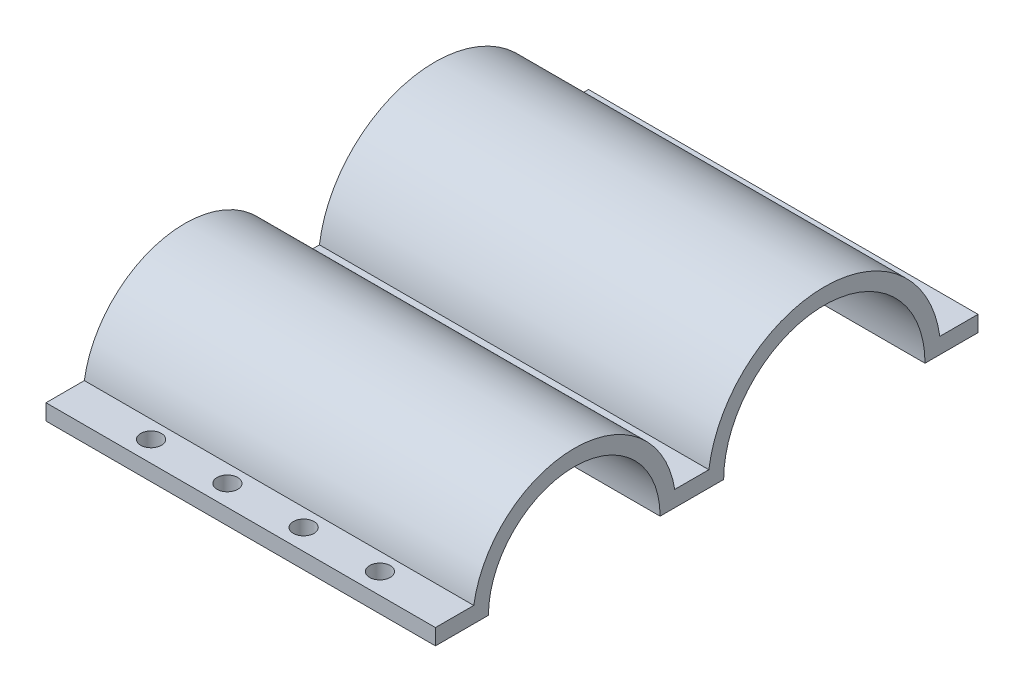
SolidWorks part; units mm, degrees
ref_plane "Front Plane" through (0, 0, 0) normal (0, 0, 1) x (1, 0, 0)
ref_plane "Top Plane" through (0, 0, 0) normal (0, 1, 0) x (1, 0, 0)
ref_plane "Right Plane" through (0, 0, 0) normal (1, 0, 0) x (0, 0, -1)
sketch "Sketch2" plane through (0, 0, 0) normal (1, 0, 0) x (0, 0, -1)
  line L0 (0, 0) -> (-10, 0)
  line L1 (-102.4, 0) -> (-102.4, 3)
  line L3 (0, 3) -> (0, 0)
  line L4 (-48, 0) -> (-60, 0)
  line L5 (-92.4, 0) -> (-102.4, 0)
  line L6 (0, 3) -> (-7.2055, 3)
  line L7 (-50.7945, 3) -> (-57.2358, 3)
  line L8 (-95.1642, 3) -> (-102.4, 3)
  arc A0 (-60, 0) -> (-92.4, 0) centre (-76.2, 0) ccw
  arc A1 (-10, 0) -> (-48, 0) centre (-29, 0) ccw
  arc A2 (-7.2055, 3) -> (-50.7945, 3) centre (-29, 0) ccw
  arc A3 (-57.2358, 3) -> (-95.1642, 3) centre (-76.2, 0) ccw
  dimension "D2" = 16.2
  dimension "D4" = 19
  dimension "D3" = 10
  dimension "D1" = 12
  dimension "D6" = 3
extrude "Boss-Extrude1" add sketch "Sketch2" along normal blind 73.5
sketch "Sketch3" plane through (0, 3, 0) normal (0, 1, 0) x (1, 0, 0)
  line L1 (73.5, 0) -> (0, 0) construction
  line L2 (73.5, -3.93) -> (1.5, -3.93) construction
  line L6 (73.5, -102.4) -> (0, -102.4) construction
  line L7 (0, -60) -> (0, -48) construction
  line L8 (0, -54) -> (85.8213, -54) construction
  line L9 (0, -98.47) -> (85.8213, -98.47) construction
  line L10 (0, -60) -> (0, -48) construction
  circle A0 centre (15.9, -3.93) radius 1.95
  circle A1 centre (30.3, -3.93) radius 1.95
  circle A2 centre (44.7, -3.93) radius 1.95
  circle A3 centre (59.1, -3.93) radius 1.95
  circle A4 centre (15.9, -54) radius 1.95
  circle A5 centre (30.3, -54) radius 1.95
  circle A6 centre (44.7, -54) radius 1.95
  circle A7 centre (59.1, -54) radius 1.95
  circle A8 centre (15.9, -98.47) radius 1.95
  circle A9 centre (30.3, -98.47) radius 1.95
  circle A10 centre (44.7, -98.47) radius 1.95
  circle A11 centre (59.1, -98.47) radius 1.95
  point P40 (0, -54)
  dimension "D1" = 3.9
  dimension "D4" = 14.4
  dimension "D5" = 14.4
  dimension "D6" = 14.4
  dimension "D2" = 72
  dimension "D3" = 14.4
  dimension "D7" = 3.93
  dimension "D8" = 3.93
extrude "Cut-Extrude1" cut sketch "Sketch3" against normal up to surface (3 mm away) up to face at (36.75, 0, 97.4)
equation "\"MotorDIA\"= 37'ME 405 Motor Diameter"
equation "\"SyringeDIA\"= 31.4'60ml Syringe Diameter"
equation "\"MotorShaftDIA\"= 6'Motor Shaft Dia"
equation "\"MotorKeyway\"= 1'ME 405 Motor Shaft Keyway Depth"
equation "\"MotorLength\"= 67.5'ME 405 Motor Length Excluding Shaft"
equation "\"SyringeLength\"= 117.3'60ml Syringe Length Excluding Nozzle"
equation "\"3Dtol\"= .5'Sizing Tolerance for 3D printed parts"
equation "\"ChamberDIA\"= 100 - 4'Buoyancy Chamber inner Diameter"
equation "\"ChamberThk\"= 2mm'Buoyancy Chamber Wall Thickness"
equation "\"BearingOD\"= 10"
equation "\"BearingID\"= 4"
equation "\"Bearingwidth\"= 4"
equation "\"ShaftDIA\"= 4"
equation "\"D1@Boss-Extrude1\"=\"MotorLength\"+6"
equation "\"D4@Sketch3\"=\"D3@Sketch3\""
equation "\"D5@Sketch3\"=\"D3@Sketch3\""
equation "\"D6@Sketch3\"=\"D3@Sketch3\""
equation "\"D3@Sketch3\"=\"D2@Sketch3\"/5"
equation "\"D2@Sketch2\"=\"SyringeDIA\"/2+\"3Dtol\""
equation "\"D4@Sketch2\"=\"MotorDIA\"/2+\"3Dtol\""
